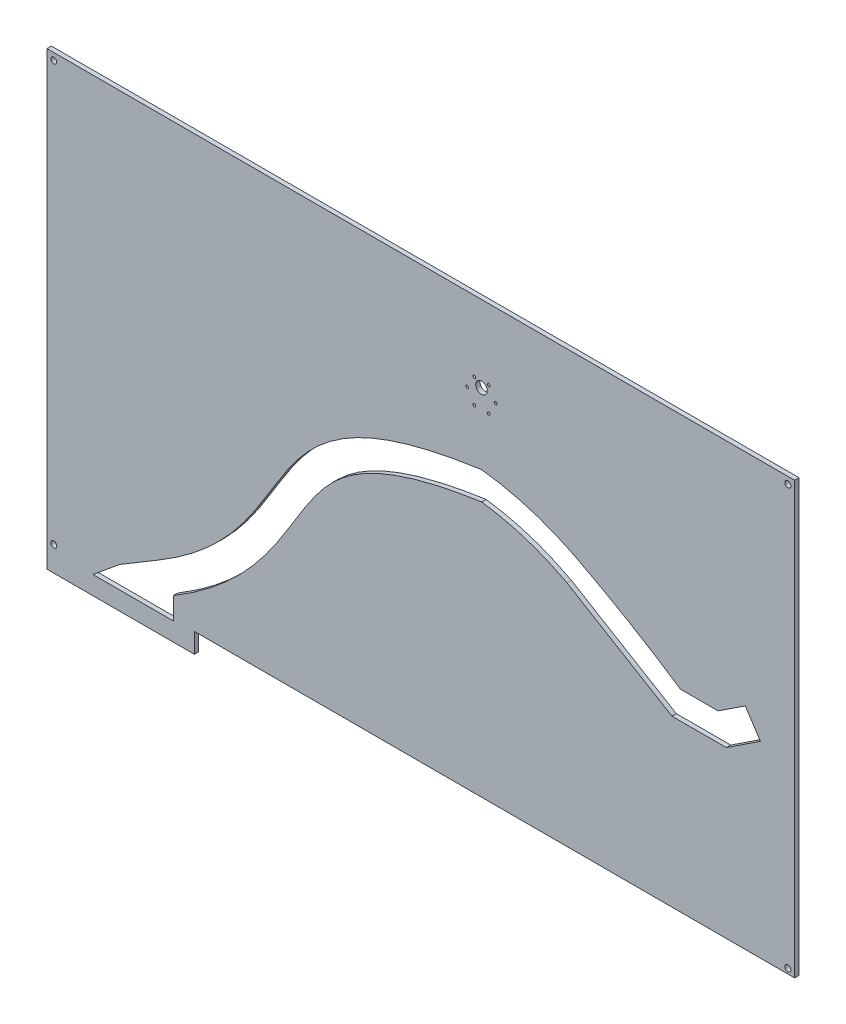
SolidWorks part; units mm, degrees
ref_plane "前视基准面" through (0, 0, 0) normal (0, 0, 1) x (1, 0, 0)
ref_plane "上视基准面" through (0, 0, 0) normal (0, 1, 0) x (1, 0, 0)
ref_plane "右视基准面" through (0, 0, 0) normal (1, 0, 0) x (0, 0, -1)
sketch "Sketch1" plane through (0, 0, 0) normal (0, 0, 1) x (1, 0, 0)
  line L0 (86.3892, 46.5642) -> (136.3892, 46.5642) construction
  line L1 (136.3892, 46.5642) -> (169.6686, 68.4983) construction
  line L2 (-475, -100) -> (-518.0311, -125.7444)
  line L3 (-459.5978, -125.7444) -> (-459.5978, -149.5504)
  line L4 (81.7745, 31.5642) -> (140.8878, 31.5642)
  line L5 (-467.2989, -112.8722) -> (-510.33, -138.6166) construction
  line L6 (140.8878, 31.5642) -> (177.9233, 55.9739)
  line L7 (-459.5978, -149.5504) -> (-546.7804, -149.5504)
  line L8 (-436.8168, -147.9944) -> (215.0808, -147.9944)
  line L9 (215.0808, -147.9944) -> (215.0808, 320)
  line L10 (215.0808, 320) -> (-596.8168, 320)
  line L11 (-596.8168, -150) -> (-596.8168, 320)
  line L12 (215.0808, -147.9944) -> (-596.8168, 320) construction
  line L13 (215.0808, 320) -> (-596.8168, -150) construction
  line L14 (-518.0311, -125.7444) -> (-459.5978, -125.7444) construction
  line L15 (-518.0311, -125.7444) -> (-546.7804, -149.5504)
  line L16 (-436.8168, -147.9944) -> (-436.8168, -169.5504)
  line L17 (90.9712, 61.5642) -> (131.8907, 61.5642)
  line L18 (-596.8168, -150) -> (-596.8168, -169.5504)
  line L19 (-596.8168, -169.5504) -> (-436.8168, -169.5504)
  line L21 (-32.3237, 100) -> (135.1953, 100) construction
  line L22 (-25, 130) -> (125, 130) construction
  line L23 (-28.6108, 115) -> (130.0228, 115) construction
  line L24 (131.8907, 61.5642) -> (161.4139, 81.0227)
  line L25 (177.9233, 55.9739) -> (161.4139, 81.0227)
  line L26 (-21.7014, 128.3139) -> (-25, 130)
  line L27 (-32.3237, 100) -> (81.7745, 31.5642)
  arc A0 (-125, 160) -> (-25, 130) centre (-159.8893, -137.9643) cw
  arc A1 (-28.6108, 115) -> (86.3892, 46.5642) centre (-559.3589, -907.7137) cw construction
  arc A2 (-124.7147, 129.7347) -> (-32.3237, 100) centre (-159.8893, -137.9643) cw
  circle A3 centre (-125, 230) radius 15.5 construction
  arc A4 (-124.84, 144.8723) -> (-28.6108, 115) centre (-159.8893, -137.9643) cw construction
  arc A5 (-21.7014, 128.3139) -> (90.9712, 61.5642) centre (-559.3589, -907.7137) cw
  circle A6 centre (-589.3757, -142.5578) radius 3.2924
  circle A7 centre (207.6422, -142.5578) radius 3.2924
  circle A8 centre (207.6422, 312.5578) radius 3.2944
  circle A9 centre (-589.3757, 312.5578) radius 3.1635
  arc A10 (135.1953, 100) -> (187.8618, 132.897) centre (303.6181, -111.0302) cw construction
  arc A11 (130.0228, 115) -> (181.4309, 146.4485) centre (303.6181, -111.0302) cw construction
  arc A12 (125, 130) -> (175, 160) centre (303.6181, -111.0302) cw construction
  arc A13 (-35.5202, 101.6861) -> (81.7745, 31.5642) centre (-559.3589, -907.7137) cw construction
  circle A14 centre (-140.5, 230) radius 1.5
  circle A15 centre (-132.75, 243.4234) radius 1.5
  circle A16 centre (-117.25, 243.4234) radius 1.5
  circle A17 centre (-109.5, 230) radius 1.5
  circle A18 centre (-117.25, 216.5766) radius 1.5
  circle A19 centre (-132.75, 216.5766) radius 1.5
  circle A20 centre (-125, 237) radius 6.25
  spline S0 degree 3 poles (-475, -100) (-419.5406, -66.8201) (-329.5908, 43.116) (-307.6356, 134.2871) (-125, 160) knots 0 0 0 0 0.312224 1 1 1 1
  spline S1 degree 1 poles (-459.5978, -125.7444) (-124.7147, 129.7347) knots 0 0 1 1 construction
  spline S2 degree 3 poles (-459.5978, -125.7444) (-458.1292, -124.8657) (-455.1858, -123.0815) (-449.4714, -119.5247) (-442.5555, -115.0462) (-434.6362, -109.6397) (-424.5564, -102.3861) (-412.8294, -93.2453) (-400.0558, -82.1905) (-388.4865, -71.0922) (-374.5374, -56.3046) (-359.6201, -37.9792) (-344.8908, -16.7676) (-332.3401, 3.2457) (-321.0552, 21.7964) (-310.226, 38.6648) (-299.0796, 53.8348) (-286.8128, 67.5146) (-272.4318, 80.0885) (-257.6527, 89.9241) (-243.4982, 97.442) (-231.5651, 102.8866) (-218.1727, 108.1127) (-203.191, 113.0878) (-189.2817, 116.9961) (-177.2434, 119.9629) (-167.7458, 122.1041) (-157.766, 124.1573) (-149.0369, 125.7919) (-141.7993, 127.0518) (-136.2431, 127.9723) (-131.5022, 128.7191) (-127.6487, 129.3032) (-125.6903, 129.5925) (-124.7147, 129.7347) knots 0 0 0 0 0.007773 0.015545 0.03109 0.046636 0.062181 0.093271 0.124361 0.155452 0.186542 0.248723 0.310904 0.373084 0.435265 0.497446 0.559626 0.621807 0.683988 0.746169 0.777259 0.808349 0.83944 0.87053 0.90162 0.917166 0.932711 0.948256 0.963801 0.971574 0.979346 0.987119 0.991005 0.994892 0.994892 0.994892 0.994892
  spline S3 degree 1 poles (-467.2989, -112.8722) (-124.84, 144.8723) knots 0 0 1 1 construction
  spline S4 degree 3 poles (-467.2989, -112.8722) (-465.8766, -112.0213) (-463.025, -110.2926) (-457.4973, -106.8516) (-450.8174, -102.5249) (-443.1848, -97.3122) (-433.4896, -90.3317) (-422.2436, -81.559) (-410.0336, -70.981) (-398.9994, -60.3828) (-385.707, -46.2708) (-371.4731, -28.7597) (-357.2741, -8.2881) (-344.9599, 11.3612) (-333.6257, 29.9919) (-322.417, 47.4318) (-310.4985, 63.6121) (-297.0179, 78.5777) (-281.0248, 92.4603) (-264.7088, 103.2127) (-249.3105, 111.3089) (-236.4572, 117.1105) (-222.1723, 122.621) (-206.3349, 127.8161) (-191.7467, 131.8615) (-179.1859, 134.915) (-169.3063, 137.1107) (-158.9544, 139.2089) (-149.9221, 140.8739) (-142.4479, 142.1541) (-136.7117, 143.0887) (-130.8627, 143.9946) (-126.8382, 144.5862) (-124.84, 144.8723) knots 0 0 0 0 0.007793 0.015586 0.031173 0.046759 0.062345 0.093518 0.12469 0.155863 0.187036 0.249381 0.311726 0.374071 0.436417 0.498762 0.561107 0.623452 0.685798 0.748143 0.779315 0.810488 0.841661 0.872833 0.904006 0.919592 0.935179 0.950765 0.966351 0.974144 0.981937 0.989731 0.997524 0.997524 0.997524 0.997524 construction
  point P38 (-190, 85.5025)
  point P62 (-125, 230)
  dimension "D5" = 300
  dimension "D8" = 15
  dimension "D14" = 470
  dimension "D22" = 651.8975
  dimension "D23" = 70
  dimension "D24" = 100
  dimension "D26" = 6
  dimension "D27" = 3
  dimension "D1" = 105
  dimension "D2" = 100
  dimension "D3" = 350
  dimension "D4" = 260
  dimension "D6" = 100
  dimension "D7" = 30
  dimension "D9" = 15
  dimension "D10" = 115
  dimension "D11" = 50
  dimension "D13" = 15
  dimension "D15" = 190
  dimension "D16" = 320
  dimension "D17" = 20
  dimension "D25" = 811.9
  dimension "D12" = 30
extrude "Boss-Extrude1" add sketch "Sketch1" along normal blind 4.7625
